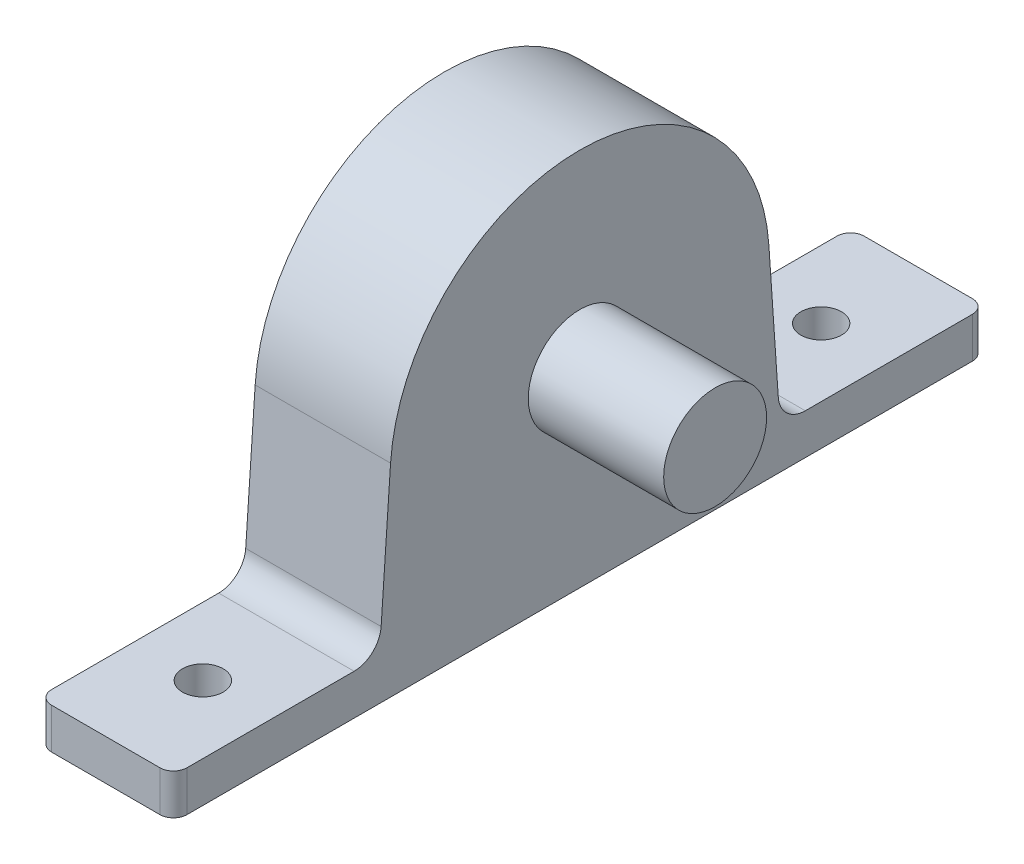
SolidWorks part; units mm, degrees
ref_plane "Front Plane" through (0, 0, 0) normal (0, 0, 1) x (1, 0, 0)
ref_plane "Top Plane" through (0, 0, 0) normal (0, 1, 0) x (1, 0, 0)
ref_plane "Right Plane" through (0, 0, 0) normal (1, 0, 0) x (0, 0, -1)
sketch "Sketch1" plane through (0, 0, 0) normal (1, 0, 0) x (0, 0, -1)
  line L0 (-15, 0) -> (15, 0)
  line L1 (-15, 0) -> (-9.5209, 17.0581)
  line L2 (9.5209, 17.0581) -> (15, 0)
  line L3 (0, 3) -> (-11, 3) construction
  line L4 (0, 25) -> (9.5209, 25) construction
  line L5 (0, 28) -> (15, 28) construction
  line L6 (-15, 0) -> (-13.5737, 20.6565) construction
  line L7 (0, 14) -> (0, 0) construction
  line L8 (15, 0) -> (13.5737, 20.6565) construction
  arc A0 (-9.5209, 17.0581) -> (9.5209, 17.0581) centre (0, 14) cw
  circle A1 centre (0, 14) radius 11 construction
  arc A2 (-12.5173, 7.7296) -> (13.1196, 9.1136) centre (0, 14) ccw construction
  arc A3 (13.9667, 14.9644) -> (-13.9667, 14.9644) centre (0, 14) ccw construction
  point P4 (0, 0)
  point P15 (7.5, 28)
  dimension "D2" = 10
  dimension "D4" = 22
  dimension "D1" = 30
  dimension "D3" = 14
  dimension "D5" = 3
extrude "Boss-Extrude1" add sketch "Sketch1" along normal blind 10
sketch "Sketch2" plane through (10, 0, 0) normal (1, 0, 0) x (0, 0, -1)
  circle A0 centre (0, 14) radius 3.8
  dimension "D1" = 7.6
extrude "Boss-Extrude2" add sketch "Sketch2" along normal blind 10
sketch "Sketch4" plane through (10, 0, 0) normal (1, 0, 0) x (0, 0, -1)
  line L0 (15, 0) -> (13.5737, 20.6565) construction
  line L1 (-15, 0) -> (-13.5737, 20.6565) construction
  line L2 (15, 0) -> (13.5737, 20.6565)
  line L3 (-15, 0) -> (15, 0)
  line L4 (15, 0) -> (9.5209, 17.0581)
  line L5 (-9.5209, 17.0581) -> (-15, 0)
  line L6 (-15, 0) -> (15, 0)
  line L7 (15, 0) -> (9.5209, 17.0581)
  line L8 (-9.5209, 17.0581) -> (-15, 0)
  line L9 (-15, 0) -> (-13.5737, 20.6565)
  arc A0 (13.9667, 14.9644) -> (-13.9667, 14.9644) centre (0, 14) ccw construction
  arc A1 (9.5209, 17.0581) -> (-9.5209, 17.0581) centre (0, 14) ccw
  arc A2 (9.5209, 17.0581) -> (-9.5209, 17.0581) centre (0, 14) ccw
  arc A3 (13.9667, 14.9644) -> (-13.9667, 14.9644) centre (0, 14) ccw
  arc M6 (9.5209, 17.0581) -> (-9.5209, 17.0581) centre (0, 14) ccw
  line M7 (-9.5209, 17.0581) -> (-15, 0)
  line M9 (15, 0) -> (9.5209, 17.0581)
  dimension "D1" = 0
extrude "Boss-Extrude3" add sketch "Sketch4" against normal up to surface (10 mm away) contours L2 A3 L9 M7 M6 M9 region at (10, 8.6546, -12.6512) up to face at (0, 10.2645, 0)
sketch "Sketch5" plane through (0, 0, 0) normal (0, -1, 0) x (1, 0, 0)
  line L0 (10, 15) -> (10, -15) construction
  line L1 (0, 30) -> (10, 30)
  line L2 (0, 30) -> (0, -30)
  line L3 (0, -30) -> (10, -30)
  line L4 (10, 30) -> (10, -30)
  line L5 (0, 15) -> (0, -15) construction
  point P4 (0, 32.8263)
  point P9 (0, 0)
  dimension "D1" = 60
extrude "Boss-Extrude4" add sketch "Sketch5" against normal blind 3
fillet "Fillet1" radius 1 4 edges at (0, 1.5, -30) (0, 1.5, 30) (10, 1.5, 30) (10, 1.5, -30)
fillet "Fillet2" radius 2 2 edges at (5, 3, -14.7929) (5, 3, 14.7929)
sketch "Sketch7" plane through (0, 3, 0) normal (0, 1, 0) x (1, 0, 0)
  line L0 (1, 30) -> (9, 30) construction
  line L1 (0, -29) -> (0, -16.6595) construction
  line L2 (0, 16.6595) -> (0, 29) construction
  circle A0 centre (5, 22.8298) radius 1.5
  circle A1 centre (5, -22.8298) radius 1.5
  point P6 (5, 30)
  point P9 (0, -22.8298)
  point P12 (0, 22.8298)
  dimension "D1" = 3
extrude "Cut-Extrude1" cut sketch "Sketch7" against normal blind 3
